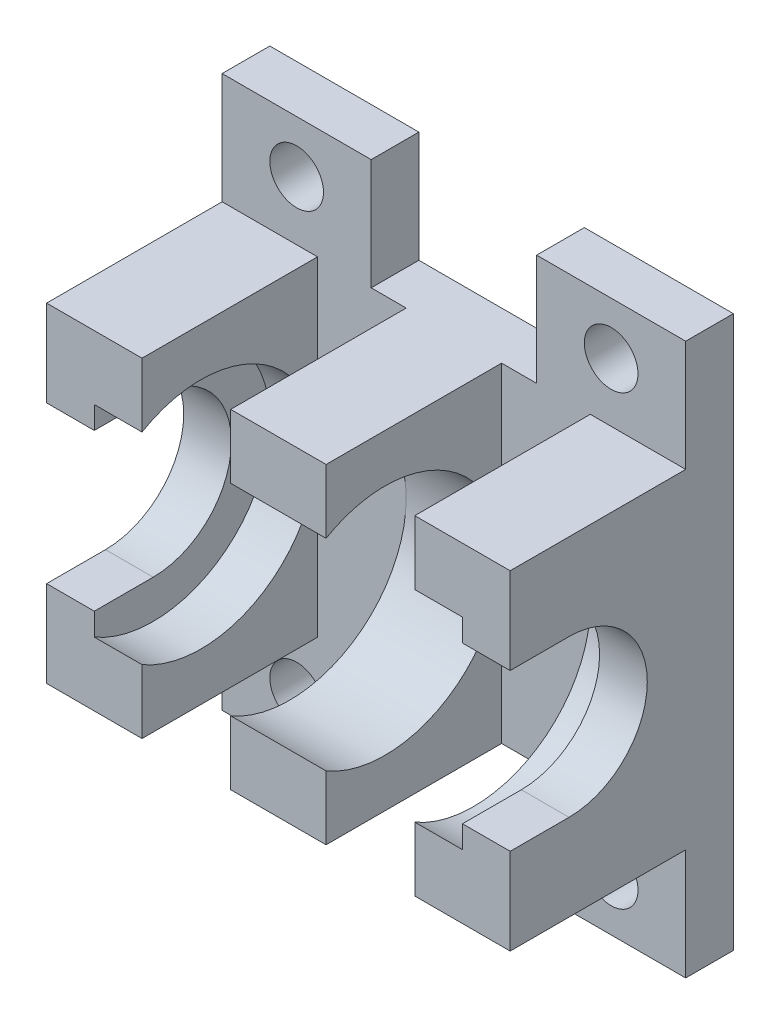
SolidWorks part; units mm, degrees
ref_plane "Piano frontale" through (0, 0, 0) normal (0, 0, 1) x (1, 0, 0)
ref_plane "Piano superiore" through (0, 0, 0) normal (0, 1, 0) x (1, 0, 0)
ref_plane "Piano destro" through (0, 0, 0) normal (1, 0, 0) x (0, 0, -1)
sketch "Schizzo1" plane through (0, 0, 0) normal (0, 0, 1) x (1, 0, 0)
  line L0 (0, 18.5) -> (0, -18.5) construction
  line L1 (-15.55, 11.05) -> (-15.55, 18.5)
  line L2 (15.55, -11.05) -> (15.55, 11.05)
  line L3 (-15.55, 18.5) -> (-5.55, 18.5)
  line L4 (-15.55, -11.05) -> (-15.55, 11.05)
  line L5 (15.55, -11.05) -> (-15.55, 11.05) construction
  line L6 (15.55, 11.05) -> (-15.55, -11.05) construction
  line L7 (-5.55, 18.5) -> (-5.55, 11.05)
  line L8 (-5.55, 11.05) -> (5.55, 11.05)
  line L9 (-15.55, 11.05) -> (-5.55, 11.05) construction
  line L10 (-10.55, 11.05) -> (-10.55, 18.5) construction
  line L11 (5.55, 18.5) -> (5.55, 11.05)
  line L12 (15.55, 18.5) -> (5.55, 18.5)
  line L13 (15.55, 11.05) -> (15.55, 18.5)
  line L14 (15.55, -11.05) -> (15.55, -18.5)
  line L15 (15.55, -18.5) -> (5.55, -18.5)
  line L16 (5.55, -18.5) -> (5.55, -11.05)
  line L17 (-15.55, 0) -> (15.55, 0) construction
  line L18 (-5.55, -11.05) -> (5.55, -11.05)
  line L19 (-5.55, -18.5) -> (-5.55, -11.05)
  line L20 (-15.55, -18.5) -> (-5.55, -18.5)
  line L21 (-15.55, -11.05) -> (-15.55, -18.5)
  circle A0 centre (-10.55, 15) radius 1.8
  circle A1 centre (10.55, 15) radius 1.8
  circle A2 centre (10.55, -15) radius 1.8
  circle A3 centre (-10.55, -15) radius 1.8
  point P0 (0, 0)
  point P21 (0, 11.05)
  dimension "D5" = 3.5
  dimension "D6" = 3.6
  dimension "D1" = 22.1
  dimension "D2" = 31.1
  dimension "D3" = 10
  dimension "D4" = 7.45
extrude "Base" add sketch "Schizzo1" along normal blind 3.2
sketch "Schizzo2" plane through (0, 0, 3.2) normal (0, 0, 1) x (1, 0, 0)
  line L0 (-15.55, 18.5) -> (-15.55, -18.5) construction
  line L1 (-9.15, -11.05) -> (-3.2, -11.05) construction
  line L2 (3.2, -11.05) -> (9.15, -11.05) construction
  line L3 (-9.15, 11.05) -> (-3.2, 11.05) construction
  line L4 (-15.55, -11.05) -> (-9.15, -11.05)
  line L5 (-15.55, -11.05) -> (-15.55, 11.05)
  line L6 (-15.55, 11.05) -> (-9.15, 11.05)
  line L7 (-9.15, -11.05) -> (-9.15, 11.05)
  line L8 (5.55, 11.05) -> (-5.55, 11.05) construction
  line L9 (-3.2, -11.05) -> (3.2, -11.05)
  line L10 (-3.2, -11.05) -> (-3.2, 11.05)
  line L11 (-3.2, 11.05) -> (3.2, 11.05)
  line L12 (3.2, -11.05) -> (3.2, 11.05)
  line L13 (3.2, 11.05) -> (9.15, 11.05) construction
  line L15 (-3.2, -11.05) -> (3.2, 11.05) construction
  line L16 (-3.2, 11.05) -> (3.2, -11.05) construction
  line L17 (15.55, -18.5) -> (15.55, 18.5) construction
  line L18 (15.55, 11.05) -> (9.15, 11.05)
  line L19 (15.55, 11.05) -> (15.55, -11.05)
  line L20 (15.55, -11.05) -> (9.15, -11.05)
  line L21 (9.15, 11.05) -> (9.15, -11.05)
  point P6 (0, 0)
  dimension "D1" = 6.4
extrude "Stand-off" add sketch "Schizzo2" along normal blind 11.775
sketch "Schizzo3" plane through (0, 0, 0) normal (1, 0, 0) x (0, 0, -1)
  line L0 (-14.975, 11.05) -> (-14.975, -11.05) construction
  line L1 (-14.975, 11.05) -> (-14.975, -11.05) construction
  line L2 (-11.026, 0) -> (-14.975, 0) construction
  line L5 (-3.2, 11.05) -> (-3.2, -11.05) construction
  line L6 (-11.026, 0) -> (-3.2, 0) construction
  line L7 (-3.2, 11.05) -> (-3.2, -11.05) construction
  circle A0 centre (-11.026, 0) radius 7.826
  dimension "D1" = 15.652
extrude "Bearing slot" cut sketch "Schizzo3" against normal mid plane 24.7
sketch "Schizzo4" plane through (-15.55, 0, 0) normal (-1, 0, 0) x (0, 0, 1)
  line L0 (11.026, 5.25) -> (11.026, -5.25) construction
  line L1 (11.026, 5.25) -> (14.975, 5.25)
  line L2 (14.975, 11.05) -> (14.975, -11.05) construction
  line L4 (14.975, 5.25) -> (14.975, -5.25)
  line L5 (14.975, -5.25) -> (11.026, -5.25)
  arc A0 (14.975, 6.7566) -> (3.2, 0) centre (11.026, 0) ccw construction
  arc A1 (3.2, 0) -> (14.975, -6.7566) centre (11.026, 0) ccw construction
  arc A2 (14.975, 6.7566) -> (3.2, 0) centre (11.026, 0) ccw construction
  arc A4 (3.2, 0) -> (14.975, -6.7566) centre (11.026, 0) ccw construction
  arc A6 (11.026, 5.25) -> (11.026, -5.25) centre (11.026, 0) ccw
  dimension "D1" = 10.5
extrude "Shaft holes" cut sketch "Schizzo4" against normal up to surface (31.1 mm away) contours L5 A6 L1 L4 up to face at (15.55, 0, 5.3438)
ref_axis "Bearing axis" through (-3.2, 0, 11.026) along (1, 0, 0)
